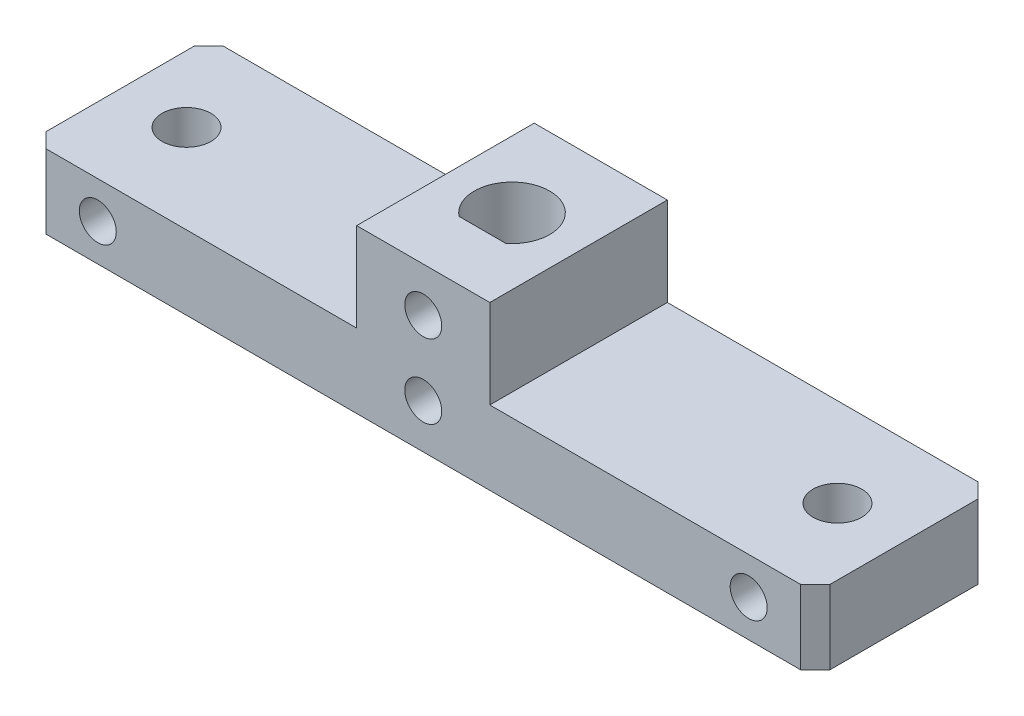
SolidWorks part; units mm, degrees
ref_plane "Top" through (0, 0, 0) normal (0, 0, 1) x (1, 0, 0)
ref_plane "Front" through (0, 0, 0) normal (0, 1, 0) x (1, 0, 0)
ref_plane "Right" through (0, 0, 0) normal (1, 0, 0) x (0, 0, -1)
sketch "Body Sketch" plane through (0, 0, 0) normal (0, 0, 1) x (1, 0, 0)
  line L0 (-26.5, 0) -> (26.5, 0)
  line L1 (26.5, 0) -> (26.5, 5)
  line L2 (26.5, 5) -> (4.5, 5)
  line L3 (4.5, 5) -> (4.5, 11)
  line L4 (4.5, 11) -> (-4.5, 11)
  line L5 (-4.5, 11) -> (-4.5, 5)
  line L6 (-4.5, 5) -> (-26.5, 5)
  line L7 (-26.5, 5) -> (-26.5, 0)
  point P8 (0, 0)
  dimension "D1" = 53
  dimension "D2" = 9
  dimension "D3" = 5
  dimension "D4" = 6
extrude "Body Extrude" add sketch "Body Sketch" against normal blind 12
sketch "Sketch2" plane through (0, 0, 0) normal (0, 1, 0) x (1, 0, 0)
  line L0 (-22.5, 6) -> (22.5, 6) construction
  line L1 (-1.5819, 4) -> (1.5819, 4)
  line L2 (0, 4) -> (0, 8.55) construction
  arc A2 (1.5819, 4) -> (-1.5819, 4) centre (0, 6) ccw
  point P8 (0, 6)
  dimension "D3" = 5.1
  dimension "D1" = 6
  dimension "D2" = 45
  dimension "D4" = 4.55
hole_wizard "Pivot M4 Holes" positions "Sketch5" profile "Sketch6" tap size "M4x0.7" standard "ANSI Metric" end condition up to next
sketch "Sketch5" plane through (0, 0, 0) normal (0, 1, 0) x (1, 0, 0)
  line L0 (-22, 6) -> (22, 6) construction
  line L2 (0, 0) -> (0, 6) construction
  point P0 (-22, 6)
  point P2 (22, 6)
  dimension "Hole Spacing" = 44
  dimension "D2" = 6
cosmetic thread "Hole Thread1" parameters "D2"=4
cosmetic thread "Hole Thread2" parameters "D2"=4
sketch "Sketch6" plane through (-22, 0, -6) normal (1, 0, 0) x (0, 0, -1)
  line L0 (0, 0) -> (0, 5)
  line L1 (0, 5) -> (1.65, 5)
  line L2 (1.65, 5) -> (1.65, 0)
  line L5 (1.65, 0) -> (0, 0)
  line L11 (0, -6.35) -> (0, 107.95) construction
  dimension "Thru Tap Drill Dia." = 3.3
  dimension "Thru Tap Drill Depth" = 5
extrude "Pivot Access Cut" cut sketch "Sketch2" along normal through all
hole_wizard "Set Screw M3 Tapped Holes" positions "Sketch7" profile "Sketch8" tap size "M3x0.5" standard "ANSI Metric" end condition up to next
sketch "Sketch7" plane through (0, 0, 0) normal (0, 0, 1) x (1, 0, 0)
  line L0 (-26.5, 5) -> (-26.5, 0) construction
  line L1 (-26.5, 2.5) -> (26.5, 2.5) construction
  line L2 (26.5, 0) -> (26.5, 5) construction
  line L4 (0, 0) -> (0, 11) construction
  line L5 (4.5, 11) -> (-4.5, 11) construction
  point P0 (-22, 2.5)
  point P2 (22, 2.5)
  point P4 (0, 8)
  point P6 (0, 3)
  dimension "D1" = 3
  dimension "D2" = 3
  dimension "Hole Spacing" = 44
sketch "Sketch8" plane through (-22, 2.5, 0) normal (1, 0, 0) x (0, -1, 0)
  line L0 (0, 0) -> (0, 4.35)
  line L1 (0, 4.35) -> (1.25, 4.35)
  line L2 (1.25, 4.35) -> (1.25, 0)
  line L5 (1.25, 0) -> (0, 0)
  line L11 (0, -6.35) -> (0, 107.95) construction
  dimension "Thru Tap Drill Dia." = 2.5
  dimension "Thru Tap Drill Depth" = 4.35
cosmetic thread "Hole Thread3" parameters "D2"=3
cosmetic thread "Hole Thread4" parameters "D2"=3
cosmetic thread "Hole Thread5" parameters "D2"=3
cosmetic thread "Hole Thread6" parameters "D2"=3
chamfer "Corner Chamfers" distance 1 angle 45 4 edges at (-26.5, 2.5, -12) (-26.5, 2.5, 0) (26.5, 2.5, -12) (26.5, 2.5, 0)
equation "\"Height\"= 12mm"
equation "\"D1@Body Extrude\"=\"Height\""
equation "\"D1@Sketch2\"=0.5*\"Height\""
equation "\"D2@Sketch5\"=0.5*\"Height\""
